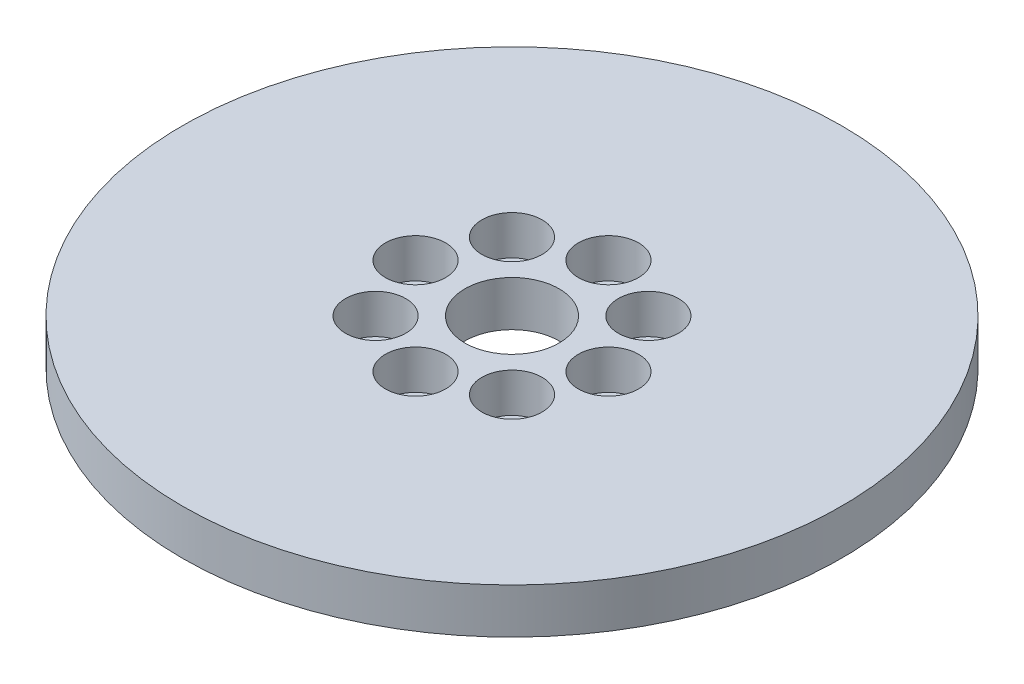
SolidWorks part; units mm, degrees
ref_plane "Front Plane" through (0, 0, 0) normal (0, 0, 1) x (1, 0, 0)
ref_plane "Top Plane" through (0, 0, 0) normal (0, 1, 0) x (1, 0, 0)
ref_plane "Right Plane" through (0, 0, 0) normal (1, 0, 0) x (0, 0, -1)
sketch "Sketch1" plane through (0, 0, 0) normal (0, 1, 0) x (1, 0, 0)
  circle A0 centre (0, 0) radius 87.5
  dimension "FLANGE_OD" = 175
extrude "Boss-Extrude1" add sketch "Sketch1" along normal blind 12
sketch "Sketch2" plane through (0, 0, 0) normal (0, 1, 0) x (1, 0, 0)
  circle A0 centre (0, 0) radius 12.5
  dimension "BORE_D" = 25
extrude "Cut-Extrude1" cut sketch "Sketch2" along normal through all
sketch "Sketch3" plane through (0, 12, 0) normal (0, 1, 0) x (1, 0, 0)
  circle A0 centre (0, 0) radius 25.6104 construction
  circle A1 centre (-25.6104, 0) radius 7.998
  dimension "BOLT_D" = 15.9959
  dimension "BOLT_PCD" = 51.2208
extrude "Cut-Extrude2" cut sketch "Sketch3" against normal blind 10.4302
pattern_circular "CirPattern1" count 8 over 360 about axis through (0, 0, 0) along (0, 1, 0) of "Cut-Extrude2"
